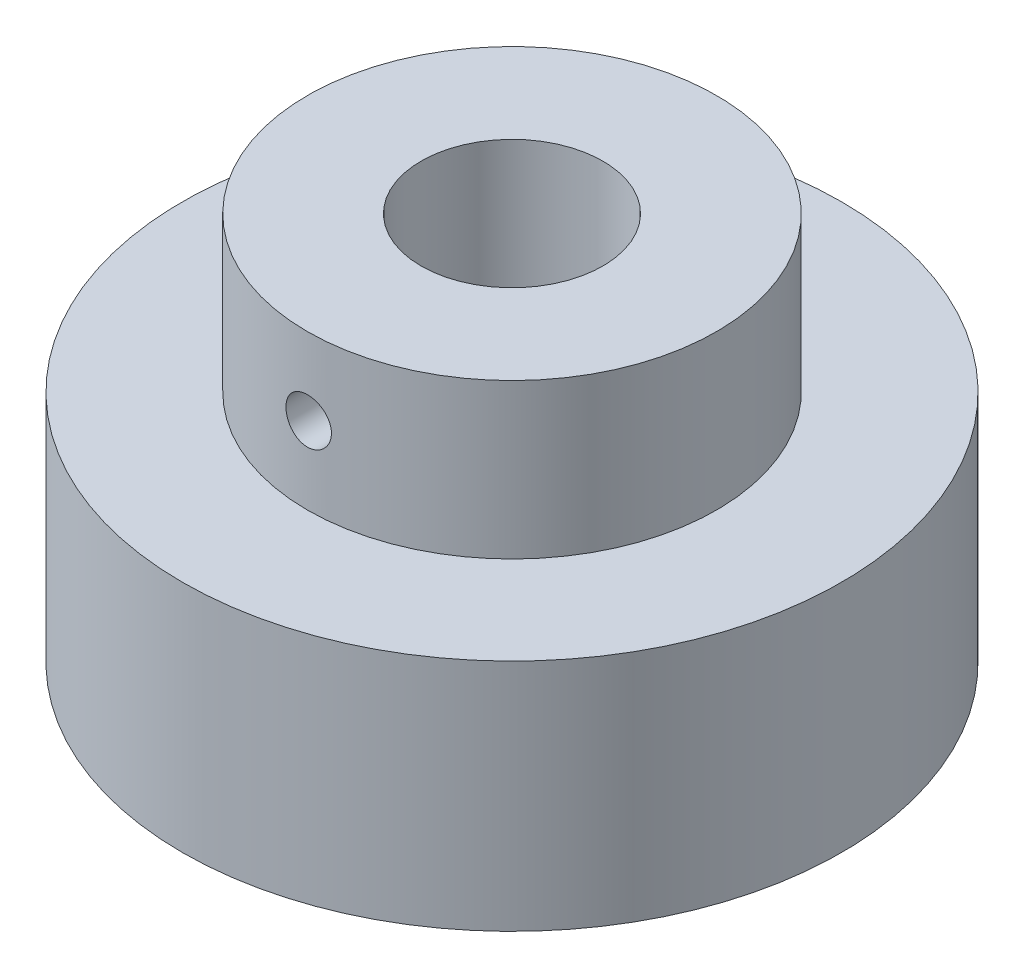
SolidWorks part; units mm, degrees
ref_plane "前基準面" through (0, 0, 0) normal (0, 0, 1) x (1, 0, 0)
ref_plane "上基準面" through (0, 0, 0) normal (0, 1, 0) x (1, 0, 0)
ref_plane "右基準面" through (0, 0, 0) normal (1, 0, 0) x (0, 0, -1)
sketch "草圖1" plane through (0, 0, 0) normal (0, 1, 0) x (1, 0, 0)
  circle A0 centre (0, 0) radius 14.5
  circle A1 centre (0, 0) radius 4
  dimension "D1" = 29
  dimension "D2" = 8
extrude "填料-伸長1" add sketch "草圖1" along normal blind 10.3
sketch "草圖2" plane through (0, 10.3, 0) normal (0, 1, 0) x (1, 0, 0)
  circle A0 centre (0, 0) radius 4 construction
  circle A1 centre (0, 0) radius 4
  circle A2 centre (0, 0) radius 9
  dimension "D1" = 18
extrude "填料-伸長2" add sketch "草圖2" along normal blind 6.8
sketch "草圖3" plane through (0, 0, 0) normal (0, 0, 1) x (1, 0, 0)
  line L0 (0, 18.1992) -> (0, -1.4413) construction
  line L1 (9, 17.1) -> (-9, 17.1) construction
  circle A0 centre (0, 13.7) radius 1
  point P5 (0, 0)
  dimension "D1" = 2
  dimension "D2" = 3.4
extrude "除料-伸長1" cut sketch "草圖3" along normal up to next
